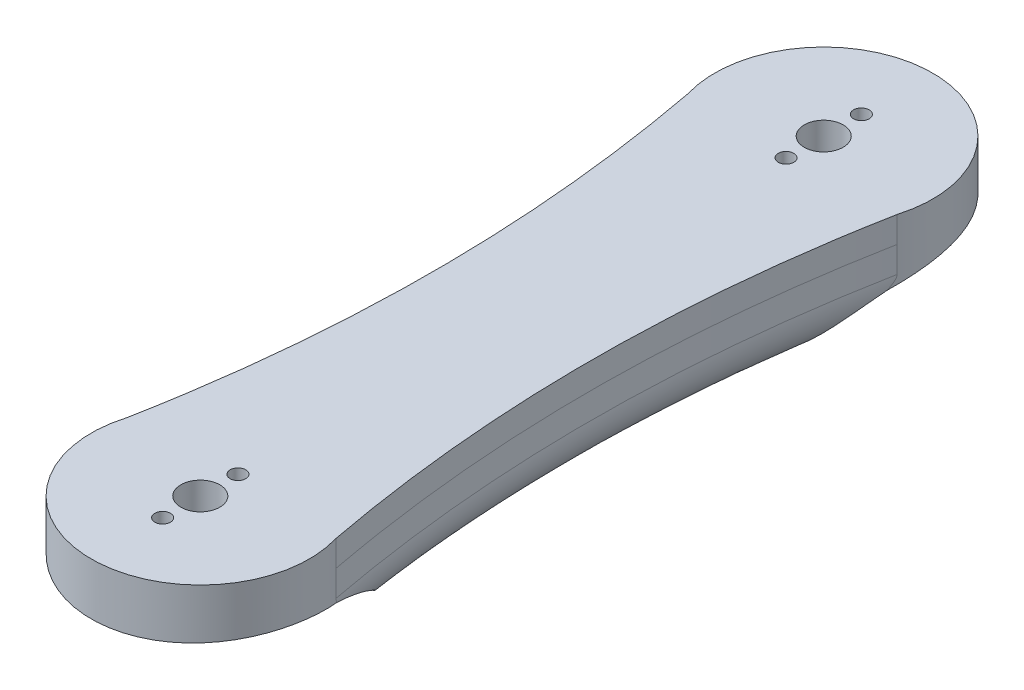
SolidWorks part; units mm, degrees
ref_plane "Front Plane" through (0, 0, 0) normal (0, 0, 1) x (1, 0, 0)
ref_plane "Top Plane" through (0, 0, 0) normal (0, 1, 0) x (1, 0, 0)
ref_plane "Right Plane" through (0, 0, 0) normal (1, 0, 0) x (0, 0, -1)
sketch "Sketch1" plane through (0, 0, 0) normal (0, 1, 0) x (1, 0, 0)
  line L0 (0, 120) -> (0, 0) construction
  line L1 (-20.1246, 6) -> (20.1246, 6) construction
  line L2 (-20.1246, 114) -> (20.1246, 114) construction
  circle A0 centre (0, 0) radius 21
  circle A1 centre (0, 120) radius 21
  spline S0 degree 2 poles (-20.1246, 114) (-9.8754, 60) (-20.1246, 6) knots 0 0 0 1 1 1
  spline S1 degree 2 poles (20.1246, 114) (9.8754, 60) (20.1246, 6) knots 0 0 0 1 1 1
  point P9 (0, 60)
  dimension "D1" = 42
  dimension "D2" = 120
  dimension "D6" = 15
  dimension "D3" = 6
  dimension "D4" = 6
  dimension "D5" = 60
extrude "Boss-Extrude1" add sketch "Sketch1" along normal blind 16 contours S1 A1 S0 A0 region at (0, 0, -60)
extrude "Boss-Extrude2" add sketch "Sketch1<3>" along normal blind 21 contours A0 | A1
sketch "Sketch1<3>" plane through (0, 0, 0) normal (0, 1, 0) x (1, 0, 0) same geometry as "Sketch1"
sketch "Sketch2" plane through (0, 0, 0) normal (1, 0, 0) x (0, 0, -1)
  line L0 (-21, 0) -> (141, 0)
  line L1 (141, 0) -> (141, 11)
  line L2 (141, 0) -> (141, 21) construction
  line L3 (-21, 0) -> (-21, 11)
  line L4 (-21, 21) -> (-21, 0) construction
  spline S0 degree 3 poles (-21, 11) (-9.0159, 11.6401) (13.6865, 13.9486) (21, 0) knots 0 0 0 0 1 1 1 1
  spline S1 degree 3 poles (141, 11) (126.7638, 12.3948) (109.9476, 11.9176) (99, 0) knots 0 0 0 0 1 1 1 1
  point P13 (131.9736, 11.5777)
  point P15 (-5.09, 11.5031)
  dimension "D1" = 11
  dimension "D2" = 42
  dimension "D3" = 42
  dimension "D4" = 11
extrude "Cut-Extrude1" cut sketch "Sketch2" against normal through all both and the other way through all contours S0 L3 L0 | L1 S1 L0 region at (0, 5.2003, 2.752) region at (0, 5.0729, -123.5786)
ref_plane "Plane1" through (0, 15, 0) normal (0, 1, 0) x (1, 0, 0)
fillet "Fillet1" radius 11 2 edges
sketch "Sketch3" plane through (0, 15, 0) normal (0, 1, 0) x (1, 0, 0)
  arc A2 (-20.1246, 114) -> (20.1246, 114) centre (0, 120) ccw
  arc A3 (20.1246, 6) -> (-20.1246, 6) centre (0, 0) ccw
  arc A4 (-20.1246, 114) -> (20.1246, 114) centre (0, 120) ccw
  arc A5 (20.1246, 6) -> (-20.1246, 6) centre (0, 0) ccw
  parabola Q2 (20.1246, 6) -> (20.1246, 114) focus (157.2547, 60) apex (15, 60)
  parabola Q3 (-20.1246, 114) -> (-20.1246, 6) focus (-157.2547, 60) apex (-15, 60)
  parabola Q4 (20.1246, 6) -> (20.1246, 114) focus (157.2547, 60) apex (15, 60)
  parabola Q5 (-20.1246, 114) -> (-20.1246, 6) focus (-157.2547, 60) apex (-15, 60)
  dimension "D1" = 0
extrude "Boss-Extrude3" add sketch "Sketch3" along normal up to surface (6 mm away) up to face at (0, 21, -99)
sketch "Sketch4" plane through (0, 0, 0) normal (0, 0, 1) x (1, 0, 0)
  line L0 (0, 9) -> (0, 0) construction
  circle A0 centre (0, 9) radius 5.75
  dimension "D1" = 11.5
  dimension "D2" = 9
extrude "Cut-Extrude2" cut sketch "Sketch4" against normal blind 124
sketch "Sketch5" plane through (0, 15, 0) normal (0, 1, 0) x (1, 0, 0)
  arc A2 (17.2497, 114.8571) -> (-17.2497, 114.8571) centre (0, 120) ccw
  circle A3 centre (0, 120) radius 18
  arc A5 (-17.2497, 5.1429) -> (17.2497, 5.1429) centre (0, 0) ccw
  circle A6 centre (0, 0) radius 18
  point P0 (17.2497, 6.672)
  dimension "D1" = 3
  dimension "D2" = 3
extrude "Cut-Extrude3" cut sketch "Sketch5" against normal blind 124
sketch "Sketch6" plane through (0, 15, 0) normal (0, -1, 0) x (1, 0, 0)
  line L0 (0, 7.25) -> (0, -7.25) construction
  line L1 (0, 0) -> (0, -120) construction
  line L2 (0, -60) -> (-68.1683, -60) construction
  circle A0 centre (0, 0) radius 3.75
  circle A1 centre (0, 7.25) radius 1.5
  circle A2 centre (0, -7.25) radius 1.5
  circle A3 centre (0, -112.75) radius 1.5
  circle A4 centre (0, -120) radius 3.75
  circle A5 centre (0, -127.25) radius 1.5
  dimension "D1" = 7.5
  dimension "D2" = 3
  dimension "D3" = 3
  dimension "D4" = 7.25
extrude "Cut-Extrude4" cut sketch "Sketch6" against normal through all both and the other way through all
